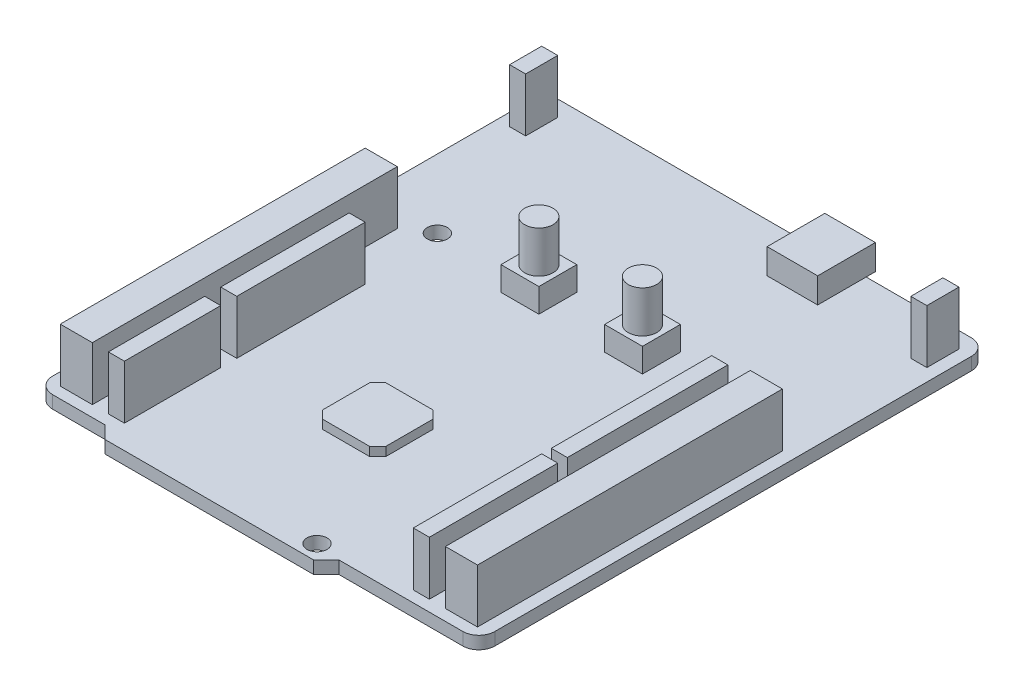
SolidWorks part; units mm, degrees
ref_plane "Front Plane" through (0, 0, 0) normal (0, 0, 1) x (1, 0, 0)
ref_plane "Top Plane" through (0, 0, 0) normal (0, 1, 0) x (1, 0, 0)
ref_plane "Right Plane" through (0, 0, 0) normal (1, 0, 0) x (0, 0, -1)
sketch "Sketch1" plane through (0, 0, 0) normal (0, 1, 0) x (1, 0, 0)
  line L1 (-35, 41.25) -> (35, 41.25)
  line L2 (-35, 41.25) -> (-35, -41.25)
  line L3 (-35, -41.25) -> (35, -41.25)
  line L4 (35, 41.25) -> (35, -41.25)
  line L5 (-35, 41.25) -> (35, -41.25) construction
  line L6 (-35, -41.25) -> (35, 41.25) construction
  point P0 (0, 0)
  dimension "D1" = 82.5
  dimension "D2" = 70
extrude "Boss-Extrude1" add sketch "Sketch1" along normal blind 2
sketch "Sketch2" plane through (0, 2, 0) normal (0, 1, 0) x (1, 0, 0)
  line L0 (-35, -41.25) -> (-35, -39.25)
  line L1 (-35, 41.25) -> (-35, -41.25) construction
  line L2 (-35, -39.25) -> (-24.13, -39.25)
  line L3 (-24.13, -39.25) -> (-22.13, -41.25)
  line L4 (-35, -41.25) -> (35, -41.25) construction
  line L5 (-22.13, -41.25) -> (-35, -41.25)
  line L6 (35, -39.25) -> (12.87, -39.25)
  line L7 (35, -41.25) -> (35, 41.25) construction
  line L8 (12.87, -39.25) -> (10.87, -41.25)
  line L9 (10.87, -41.25) -> (35, -41.25)
  line L10 (35, -41.25) -> (35, -39.25)
  line L11 (-22.13, -41.25) -> (10.87, -41.25) construction
  line L12 (27.94, 10.78) -> (33.02, 10.78)
  line L13 (-33.02, 10.78) -> (-27.94, 10.78)
  line L14 (-33.02, 10.78) -> (-33.02, -37.48)
  line L15 (-33.02, -37.48) -> (-27.94, -37.48)
  line L16 (-27.94, 10.78) -> (-27.94, -37.48)
  line L17 (27.94, 10.78) -> (27.94, -37.48)
  line L18 (27.94, -37.48) -> (33.02, -37.48)
  line L19 (33.02, 10.78) -> (33.02, -37.48)
  line L20 (-30.48, -34.94) -> (-33.02, -37.48) construction
  line L21 (-33.02, -37.48) -> (-30.48, -37.48) construction
  line L22 (-33.02, -37.48) -> (-33.02, -34.94) construction
  line L23 (-33.02, -34.94) -> (-30.48, -34.94) construction
  line L24 (-30.48, -37.48) -> (-30.48, -34.94) construction
  line L25 (-27.94, -34.94) -> (-30.48, -34.94) construction
  line L26 (-27.94, -34.94) -> (-27.94, -37.48) construction
  line L27 (-27.94, -37.48) -> (-30.48, -37.48) construction
  line L28 (-30.48, -34.94) -> (-30.48, -37.48) construction
  line L29 (30.48, -34.94) -> (33.02, -37.48) construction
  line L30 (33.02, -37.48) -> (30.48, -37.48) construction
  line L31 (33.02, -37.48) -> (33.02, -34.94) construction
  line L32 (33.02, -34.94) -> (30.48, -34.94) construction
  line L33 (30.48, -37.48) -> (30.48, -34.94) construction
  line L34 (0, 41.25) -> (0, -41.25) construction
  line L35 (35, 41.25) -> (-35, 41.25) construction
  line L36 (-27.94, -13.35) -> (27.94, -13.35) construction
  line L37 (-22.86, -37.48) -> (22.86, -37.48) construction
  line L38 (22.86, 9.76) -> (25.4, 9.76)
  line L39 (22.86, 9.76) -> (22.86, -15.64)
  line L40 (22.86, -15.64) -> (25.4, -15.64)
  line L41 (25.4, 9.76) -> (25.4, -15.64)
  line L42 (22.86, -17.16) -> (25.4, -17.16)
  line L43 (22.86, -17.16) -> (22.86, -37.48)
  line L44 (22.86, -37.48) -> (25.4, -37.48)
  line L45 (25.4, -17.16) -> (25.4, -37.48)
  line L46 (-22.86, 0.62) -> (-25.4, 0.62)
  line L47 (-22.86, 0.62) -> (-22.86, -19.7)
  line L48 (-22.86, -19.7) -> (-25.4, -19.7)
  line L49 (-25.4, 0.62) -> (-25.4, -19.7)
  line L50 (-25.4, -22.24) -> (-22.86, -22.24)
  line L51 (-25.4, -22.24) -> (-25.4, -37.48)
  line L52 (-25.4, -37.48) -> (-22.86, -37.48)
  line L53 (-22.86, -22.24) -> (-22.86, -37.48)
  line L54 (-24.13, 0.62) -> (-24.13, 41.25) construction
  line L55 (24.13, 9.76) -> (24.13, 41.25) construction
  line L56 (-33.02, 36.18) -> (-30.48, 33.64) construction
  line L57 (-33.02, 38.72) -> (-30.48, 38.72)
  line L58 (-33.02, 38.72) -> (-33.02, 33.64)
  line L59 (-33.02, 33.64) -> (-30.48, 33.64)
  line L60 (-30.48, 38.72) -> (-30.48, 33.64)
  line L61 (-33.02, 36.18) -> (-30.48, 38.72) construction
  line L63 (33.02, 38.72) -> (30.48, 38.72)
  line L64 (33.02, 38.72) -> (33.02, 33.64)
  line L65 (33.02, 33.64) -> (30.48, 33.64)
  line L66 (30.48, 38.72) -> (30.48, 33.64)
  circle A0 centre (8.89, -38.75) radius 1.5875
  circle A1 centre (24.13, 12.05) radius 1.5875
  circle A2 centre (-24.13, 13.32) radius 1.5875
  point P30 (-30.48, -37.48)
  point P34 (-31.75, -36.21)
  point P35 (31.75, -36.21)
  point P43 (0, -13.35)
  point P60 (0, -37.48)
  point P71 (-24.13, -37.48)
  point P75 (-31.75, 34.91)
  point P76 (-31.75, 37.45)
  dimension "D6" = 3.175
  dimension "D23" = 2.29
  dimension "D1" = 33
  dimension "D2" = 10.87
  dimension "D3" = 45
  dimension "D4" = 45
  dimension "D5" = 5.08
  dimension "D7" = 5.08
  dimension "D8" = 48.26
  dimension "D9" = 3.04
  dimension "D10" = 2.54
  dimension "D11" = 2.54
  dimension "D12" = 2.54
  dimension "D13" = 63.5
  dimension "D14" = 2.54
  dimension "D15" = 2.54
  dimension "D16" = 15.24
  dimension "D17" = 20.32
  dimension "D18" = 25.4
  dimension "D19" = 20.32
  dimension "D20" = 2.54
  dimension "D21" = 1.52
  dimension "D22" = 45.72
  dimension "D24" = 12.7
  dimension "D25" = 33.02
  dimension "D26" = 3.8
  dimension "D27" = 71.12
extrude "Cut-Extrude1" cut sketch "Sketch2" against normal through all contours A2 | L2 L3 L5 L0 | L9 L10 L6 L8 | A1 | A0
fillet "Fillet1" radius 2.54 4 edges at (-35, 1, -41.25) (35, 1, -41.25) (35, 1, 39.25) (-35, 1, 39.25)
extrude "Boss-Extrude2" add sketch "Sketch2<3>" along normal blind 8.5 contours L16 L13 L14 L15 | L46 L49 L48 L47 | L53 L50 L51 L52 | L19 L12 L17 L18 | L63 L66 L65 L64 | L60 L59 L58 L57 | L41 L40 L39 L38 | L43 L44 L45 L42 region at (30.48, 2, 13.35) region at (-30.48, 2, 13.35) region at (-24.13, 2, 9.54) region at (-24.13, 2, 29.86) region at (31.75, 2, -36.18)
sketch "Sketch2<3>" plane through (0, 2, 0) normal (0, 1, 0) x (1, 0, 0) same geometry as "Sketch2"
sketch "Sketch4" plane through (0, 2, 0) normal (0, 1, 0) x (1, 0, 0)
  line L1 (7.8, 42.71) -> (15.8, 42.71)
  line L2 (7.8, 42.71) -> (7.8, 33.58)
  line L3 (7.8, 33.58) -> (15.8, 33.58)
  line L4 (15.8, 42.71) -> (15.8, 33.58)
  line L5 (-22.13, -41.25) -> (10.87, -41.25) construction
  line L6 (-11, 16.25) -> (-5, 16.25)
  line L7 (-11, 16.25) -> (-11, 10.25)
  line L8 (-11, 10.25) -> (-5, 10.25)
  line L9 (-5, 16.25) -> (-5, 10.25)
  line L10 (5.4, 16.25) -> (11.4, 16.25)
  line L11 (5.4, 16.25) -> (5.4, 10.25)
  line L12 (5.4, 10.25) -> (11.4, 10.25)
  line L13 (11.4, 16.25) -> (11.4, 10.25)
  line L14 (35, -36.71) -> (35, 38.71) construction
  line L15 (32.46, 41.25) -> (-32.46, 41.25) construction
  point P4 (0, 0)
  point P18 (0, 0)
  dimension "D1" = 6
  dimension "D2" = 8
  dimension "D3" = 57.5
  dimension "D4" = 10.4
  dimension "D5" = 23.6
  dimension "D6" = 19.2
  dimension "D7" = 9.13
  dimension "D8" = 1.46
extrude "Boss-Extrude3" add sketch "Sketch4" along normal blind 4 contours L1 L4 L3 L2
extrude "Boss-Extrude4" add sketch "Sketch4<3>" along normal blind 3.8 contours L9 L6 L7 L8 | L13 L10 L11 L12 region at (-8, 2, -13.25) region at (8.4, 2, -13.25)
sketch "Sketch4<3>" plane through (0, 2, 0) normal (0, 1, 0) x (1, 0, 0) same geometry as "Sketch4"
sketch "Sketch5" plane through (0, 5.8, 0) normal (0, 1, 0) x (1, 0, 0)
  line L0 (-11, 16.25) -> (-5, 10.25) construction
  line L1 (5.4, 16.25) -> (11.4, 10.25) construction
  circle A0 centre (-8, 13.25) radius 2.25
  circle A1 centre (8.4, 13.25) radius 2.25
  dimension "D1" = 4.5
extrude "Boss-Extrude5" add sketch "Sketch5" along normal blind 6.6
sketch "Sketch6" plane through (0, 2, 0) normal (0, 1, 0) x (1, 0, 0)
  line L0 (-35, 38.71) -> (-35, -36.71) construction
  line L1 (-7.6, -12.65) -> (2.4, -12.65)
  line L2 (-7.6, -12.65) -> (-7.6, -22.65)
  line L3 (-7.6, -22.65) -> (2.4, -22.65)
  line L4 (2.4, -12.65) -> (2.4, -22.65)
  line L5 (-7.6, -12.65) -> (2.4, -22.65) construction
  line L6 (-7.6, -22.65) -> (2.4, -12.65) construction
  line L7 (-22.13, -41.25) -> (10.87, -41.25) construction
  point P0 (-2.6, -17.65)
  dimension "D1" = 10
  dimension "D2" = 37.4
  dimension "D3" = 28.6
extrude "Boss-Extrude6" add sketch "Sketch6" along normal blind 1.4
chamfer "Chamfer1" distance 1.27 angle 45 4 edges at (2.4, 2.7, 22.65) (2.4, 2.7, 12.65) (-7.6, 2.7, 12.65) (-7.6, 2.7, 22.65)
